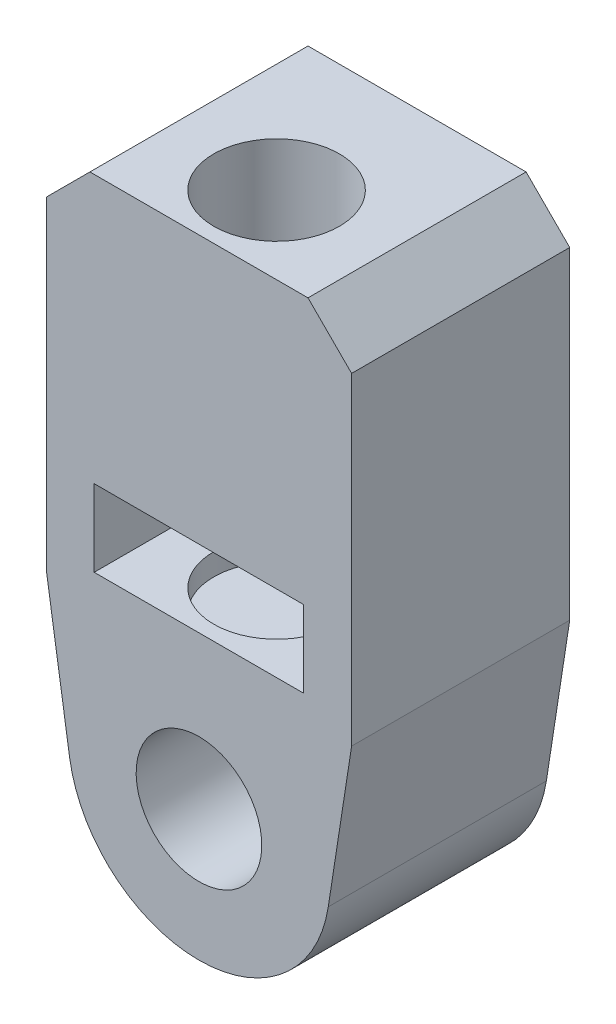
SolidWorks part; units mm, degrees
ref_plane "Front Plane" through (0, 0, 0) normal (0, 0, 1) x (1, 0, 0)
ref_plane "Top Plane" through (0, 0, 0) normal (0, 1, 0) x (1, 0, 0)
ref_plane "Right Plane" through (0, 0, 0) normal (1, 0, 0) x (0, 0, -1)
sketch "Sketch1" plane through (0, 0, 0) normal (0, 0, 1) x (1, 0, 0)
  line L0 (-5.5562, 4.7625) -> (-5.5562, 18.0975)
  line L1 (-5.5562, 18.0975) -> (5.5562, 18.0975)
  line L2 (5.5562, 18.0975) -> (5.5562, 4.7625)
  line L3 (-5.5562, 4.7625) -> (-4.7065, -0.7284)
  line L4 (4.7065, -0.7284) -> (5.5562, 4.7625)
  circle A1 centre (0, 0) radius 2.286
  arc A2 (-4.7065, -0.7284) -> (4.7065, -0.7284) centre (0, 0) ccw
  point P10 (0, 18.0975)
  dimension "D1" = 9.525
  dimension "D2" = 4.572
  dimension "D3" = 13.335
  dimension "D4" = 11.1125
  dimension "D5" = 4.7625
extrude "Boss-Extrude1" add sketch "Sketch1" along normal up to surface (7.9375 mm away)
sketch "Sketch2" plane through (0, 18.0975, 0) normal (0, 1, 0) x (1, 0, 0)
  circle A1 centre (0, -5.1125) radius 2.286
  circle A2 centre (0, -5.1125) radius 1.7525 construction
  dimension "D1" = 4.572
extrude "Cut-Extrude1" cut sketch "Sketch2" against normal offset from surface (13.335 mm away) 4.7625 up to plane "Top Plane"
sketch "Sketch3" plane through (0, 4.7625, 0) normal (0, 1, 0) x (1, 0, 0)
  line L11 (5.5562, -7.9375) -> (-5.5562, -7.9375) construction
  line L12 (-1.9064, -1.8105) -> (-3.8128, -5.1125)
  line L16 (3.8128, -5.1125) -> (1.9064, -1.8105)
  line L17 (1.9064, -1.8105) -> (-1.9064, -1.8105)
  line L18 (-3.8128, -5.1125) -> (-3.8128, -7.9375)
  line L19 (-3.8128, -7.9375) -> (3.8128, -7.9375)
  line L20 (3.8128, -7.9375) -> (3.8128, -5.1125)
  line L22 (-1.9064, -8.4145) -> (0, -8.4145) [skipped]
  line L23 (-3.8128, -5.1125) -> (-2.8596, -6.7635) [skipped]
  line L24 (2.1818, -7.9375) -> (2.8596, -6.7635) [skipped]
  circle A0 centre (0, -5.1125) radius 3.302 construction
  dimension "D1" = 6.604
extrude "Cut-Extrude2" cut sketch "Sketch3" along normal blind 2.794 from offset 0.7937
chamfer "Chamfer1" distance 1.5875 angle 45 2 edges at (5.5562, 18.0975, 3.9688) (-5.5562, 18.0975, 3.9688)
